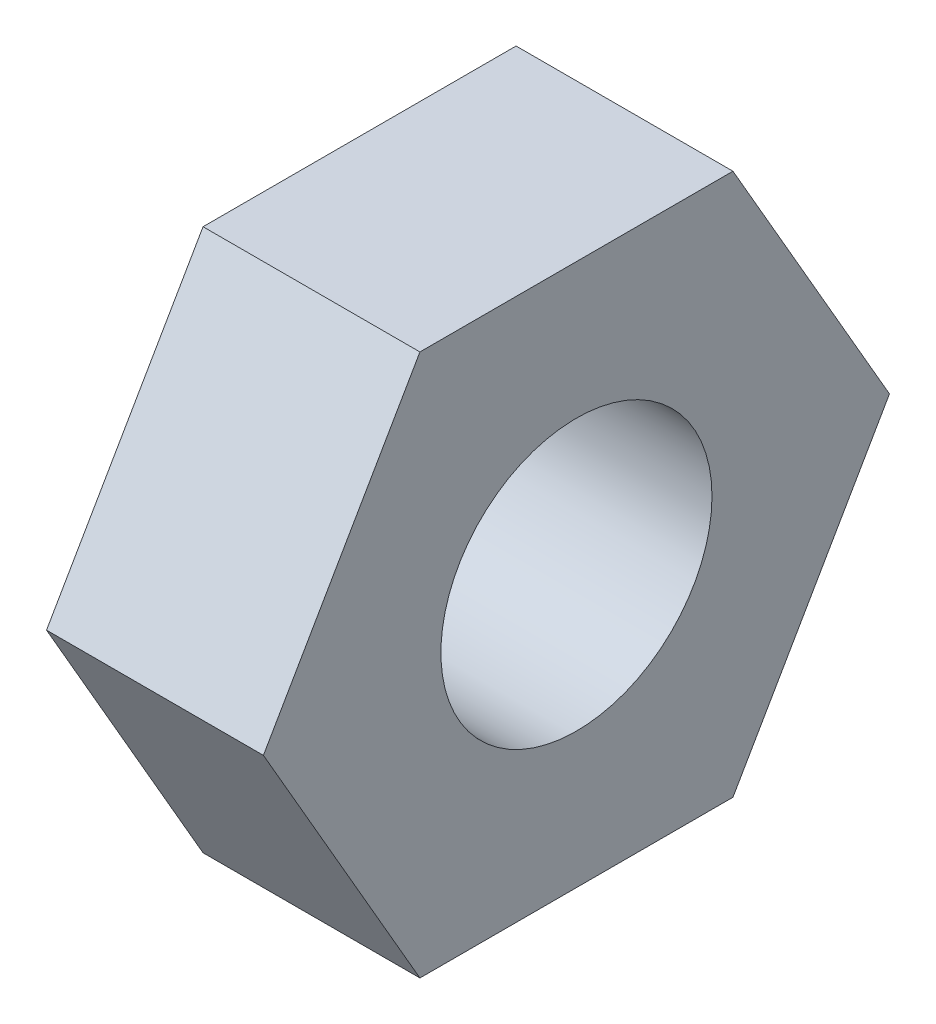
SolidWorks part; units mm, degrees
ref_plane "Front Plane" through (0, 0, 0) normal (0, 0, 1) x (1, 0, 0)
ref_plane "Top Plane" through (0, 0, 0) normal (0, 1, 0) x (1, 0, 0)
ref_plane "Right Plane" through (0, 0, 0) normal (1, 0, 0) x (0, 0, -1)
sketch "Hex Sketch" plane through (0, 0, 0) normal (1, 0, 0) x (0, 0, -1)
  line L0 (2.8868, 0) -> (1.4434, 2.5)
  line L1 (1.4434, 2.5) -> (-1.4434, 2.5)
  line L2 (-1.4434, 2.5) -> (-2.8868, 0)
  line L3 (-2.8868, 0) -> (-1.4434, -2.5)
  line L4 (-1.4434, -2.5) -> (1.4434, -2.5)
  line L5 (1.4434, -2.5) -> (2.8868, 0)
extrude "Hex" add sketch "Hex Sketch" along normal blind 2
ref_axis "Engine Axis" through (2.1, 0, 0) along (-1, 0, 0)
sketch "Bore Sketch" plane through (0, 0, 0) normal (0, 0, 1) x (1, 0, 0)
  line L0 (-400, 0) -> (400, 0) construction
  line L1 (-1, 0) -> (3, 0)
  line L2 (3, 0) -> (3, 1.25)
  line L3 (3, 1.25) -> (-1, 1.25)
  line L4 (-1, 1.25) -> (-1, 0)
revolve "Bore" cut sketch "Bore Sketch" angle 360 about L0
